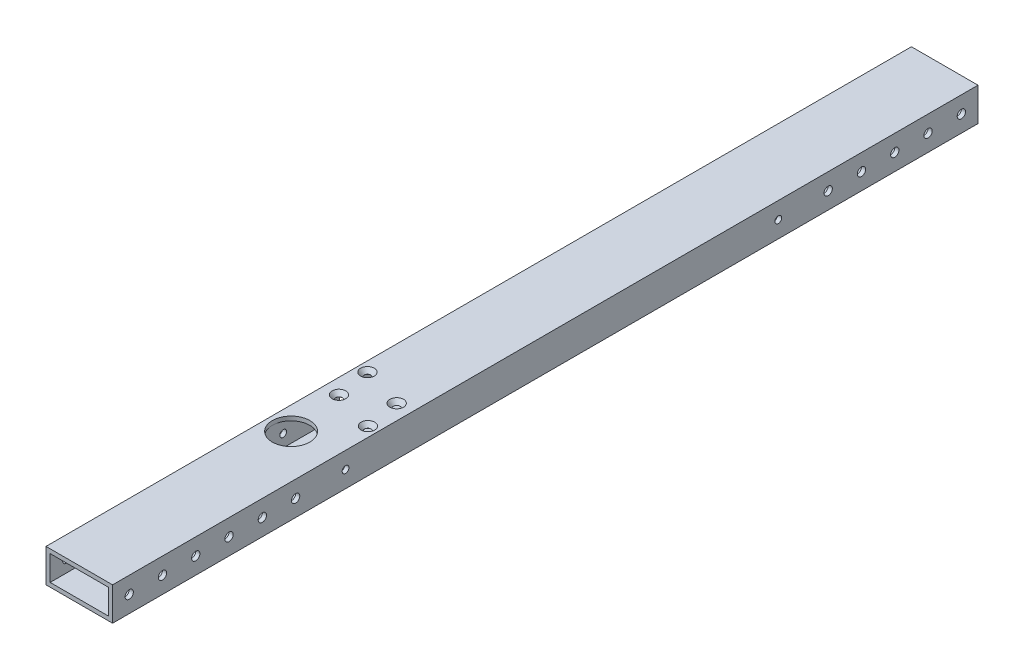
SolidWorks part; units mm, degrees
material "6061 Alloy"
ref_plane "Front Plane" through (0, 0, 0) normal (0, 0, 1) x (1, 0, 0)
ref_plane "Top Plane" through (0, 0, 0) normal (0, 1, 0) x (1, 0, 0)
ref_plane "Right Plane" through (0, 0, 0) normal (1, 0, 0) x (0, 0, -1)
sketch "Sketch1" plane through (0, 0, 0) normal (0, 0, 1) x (1, 0, 0)
  line L0 (-22.225, 9.525) -> (22.225, 9.525)
  line L2 (-25.4, 12.7) -> (25.4, 12.7)
  line L3 (-25.4, 12.7) -> (-25.4, -12.7)
  line L4 (-25.4, -12.7) -> (25.4, -12.7)
  line L5 (25.4, 12.7) -> (25.4, -12.7)
  line L10 (22.225, 9.525) -> (22.225, -9.525)
  line L11 (-22.225, -9.525) -> (22.225, -9.525)
  line L12 (-22.225, 9.525) -> (-22.225, -9.525)
  point P12 (0, 12.7)
  point P14 (25.4, 0)
  dimension "Wall Thickness" = 3.175
  dimension "Outside Width" = 50.8
  dimension "Outside Height" = 25.4
  dimension "Inside Height" = 19.05
  dimension "Inside Width" = 44.45
sketch "Sketch2" plane through (0, 0, 0) normal (1, 0, 0) x (0, 0, -1)
  line L0 (330.2, 0) -> (-330.2, 0)
  point P4 (0, 0)
  point P7 (-330.2, 0)
  point P10 (330.2, 0)
  dimension "Length" = 660.4
sketch "Sketch3" plane through (0, 0, 0) normal (0, 0, 1) x (1, 0, 0)
  line L21 (25.4, 12.7) -> (-25.4, 12.7)
  line L22 (25.4, -12.7) -> (25.4, 12.7)
  line L23 (-25.4, -12.7) -> (25.4, -12.7)
  line L24 (-25.4, 12.7) -> (-25.4, -12.7)
  line L25 (25.4, 12.7) -> (-25.4, 12.7)
  line L26 (25.4, -12.7) -> (25.4, 12.7)
  line L27 (-25.4, -12.7) -> (25.4, -12.7)
  line L28 (-25.4, 12.7) -> (-25.4, -12.7)
  line L29 (22.225, 9.525) -> (-22.225, 9.525)
  line L30 (22.225, -9.525) -> (22.225, 9.525)
  line L31 (-22.225, -9.525) -> (22.225, -9.525)
  line L32 (-22.225, 9.525) -> (-22.225, -9.525)
  line L33 (22.225, 9.525) -> (-22.225, 9.525)
  line L34 (22.225, -9.525) -> (22.225, 9.525)
  line L35 (-22.225, -9.525) -> (22.225, -9.525)
  line L36 (-22.225, 9.525) -> (-22.225, -9.525)
  dimension "D1" = 0
  dimension "D2" = 0
extrude "Boss-Extrude1" add sketch "Sketch3" along normal up to vertex (330.2 mm away) and the other way up to vertex (330.2 mm away) up to point (0, 0, 330.2) other way up to point (0, 0, -330.2)
sketch "Drawing Reference" plane through (0, 0, 0) normal (1, 0, 0) x (0, 0, -1)
  line L0 (-330.2, 0) -> (330.2, 0) construction
  line L1 (0, -12.7) -> (0, 12.7) construction
  line L2 (-330.2, -12.7) -> (330.2, -12.7) construction
  line L5 (-330.2, 12.7) -> (330.2, 12.7) construction
  point P7 (-293.624, 0)
  point P8 (293.624, 0)
  dimension "D1" = 36.576
sketch "Sketch5" plane through (25.4, 0, 0) normal (1, 0, 0) x (0, 0, -1)
  line L2 (-266.7, 0) -> (-241.3, 0)
  line L3 (-241.3, 0) -> (-215.9, 0)
  line L4 (-215.9, 0) -> (-190.5, 0)
  line L5 (-317.5, 0) -> (-330.2, 0)
  line L6 (-330.2, -12.7) -> (-330.2, 12.7) construction
  line L7 (-317.5, 0) -> (-292.1, 0)
  line L8 (-292.1, 0) -> (-266.7, 0)
sketch "Sketch8" plane through (25.4, 0, 0) normal (1, 0, 0) x (0, 0, -1)
  line L0 (330.2, 0) -> (292.1, 0)
  line L1 (330.2, -12.7) -> (330.2, 12.7) construction
  line L2 (292.1, 0) -> (266.7, 0)
  line L3 (266.7, 0) -> (241.3, 0)
  line L4 (241.3, 0) -> (215.9, 0)
  line L5 (330.2, 0) -> (317.5, 0)
hole_wizard "1/4 (0.25) Diameter Hole3" positions "Sketch12" profile "Sketch13" hole size "1/4" standard "ANSI Inch" end condition through all
sketch "Sketch12" plane through (-25.4, 0, 0) normal (-1, 0, 0) x (0, 0, 1)
  point P4 (-317.5, 0)
sketch "Sketch13" plane through (-25.4, 0, -317.5) normal (0, 1, 0) x (0, 0, 1)
  line L0 (0, 0) -> (0, 50.8)
  line L1 (0, 50.8) -> (3.175, 50.8)
  line L2 (3.175, 50.8) -> (3.175, 0)
  line L5 (3.175, 0) -> (0, 0)
  line L11 (0, -6.35) -> (0, 107.95) construction
  dimension "Thru Hole Dia." = 6.35
  dimension "Thru Hole Depth" = 50.8
hole_wizard "1/4 (0.25) Diameter Hole4" positions "Sketch14" profile "Sketch15" hole size "1/4" standard "ANSI Inch" end condition through all
sketch "Sketch14" plane through (-25.4, 0, 0) normal (-1, 0, 0) x (0, 0, 1)
  point P0 (292.1, 0)
  point P3 (317.5, 0)
sketch "Sketch15" plane through (-25.4, 0, 292.1) normal (0, 1, 0) x (0, 0, 1)
  line L0 (0, 0) -> (0, 50.8)
  line L1 (0, 50.8) -> (3.175, 50.8)
  line L2 (3.175, 50.8) -> (3.175, 0)
  line L5 (3.175, 0) -> (0, 0)
  line L11 (0, -6.35) -> (0, 107.95) construction
  dimension "Thru Hole Dia." = 6.35
  dimension "Thru Hole Depth" = 50.8
hole_wizard "1/4 (0.25) Diameter Hole5" positions "Sketch17" profile "Sketch18" hole size "1/4" standard "ANSI Inch" end condition through all
sketch "Sketch17" plane through (25.4, 0, 0) normal (1, 0, 0) x (0, 0, -1)
  point P0 (292.1, 0)
  point P3 (266.7, 0)
sketch "Sketch18" plane through (25.4, 0, -292.1) normal (0, 1, 0) x (0, 0, -1)
  line L0 (0, 0) -> (0, 50.8)
  line L1 (0, 50.8) -> (3.175, 50.8)
  line L2 (3.175, 50.8) -> (3.175, 0)
  line L5 (3.175, 0) -> (0, 0)
  line L11 (0, -6.35) -> (0, 107.95) construction
  dimension "Thru Hole Dia." = 6.35
  dimension "Thru Hole Depth" = 50.8
hole_wizard "1/4 (0.25) Diameter Hole6" positions "Sketch19" profile "Sketch20" hole size "1/4" standard "ANSI Inch" end condition through all
sketch "Sketch19" plane through (25.4, 0, 0) normal (1, 0, 0) x (0, 0, -1)
  point P0 (215.9, 0)
  point P3 (241.3, 0)
sketch "Sketch20" plane through (25.4, 0, -215.9) normal (0, 1, 0) x (0, 0, -1)
  line L0 (0, 0) -> (0, 50.8)
  line L1 (0, 50.8) -> (3.175, 50.8)
  line L2 (3.175, 50.8) -> (3.175, 0)
  line L5 (3.175, 0) -> (0, 0)
  line L11 (0, -6.35) -> (0, 107.95) construction
  dimension "Thru Hole Dia." = 6.35
  dimension "Thru Hole Depth" = 50.8
hole_wizard "1/4 (0.25) Diameter Hole7" positions "Sketch21" profile "Sketch22" hole size "1/4" standard "ANSI Inch" end condition through all
sketch "Sketch21" plane through (25.4, 0, 0) normal (1, 0, 0) x (0, 0, -1)
  point P0 (-190.5, 0)
  point P3 (-215.9, 0)
sketch "Sketch22" plane through (25.4, 0, 190.5) normal (0, 1, 0) x (0, 0, -1)
  line L0 (0, 0) -> (0, 50.8)
  line L1 (0, 50.8) -> (3.175, 50.8)
  line L2 (3.175, 50.8) -> (3.175, 0)
  line L5 (3.175, 0) -> (0, 0)
  line L11 (0, -6.35) -> (0, 107.95) construction
  dimension "Thru Hole Dia." = 6.35
  dimension "Thru Hole Depth" = 50.8
hole_wizard "1/4 (0.25) Diameter Hole8" positions "Sketch23" profile "Sketch24" hole size "1/4" standard "ANSI Inch" end condition through all
sketch "Sketch23" plane through (25.4, 0, 0) normal (1, 0, 0) x (0, 0, -1)
  point P0 (-266.7, 0)
  point P3 (-241.3, 0)
sketch "Sketch24" plane through (25.4, 0, 266.7) normal (0, 1, 0) x (0, 0, -1)
  line L0 (0, 0) -> (0, 50.8)
  line L1 (0, 50.8) -> (3.175, 50.8)
  line L2 (3.175, 50.8) -> (3.175, 0)
  line L5 (3.175, 0) -> (0, 0)
  line L11 (0, -6.35) -> (0, 107.95) construction
  dimension "Thru Hole Dia." = 6.35
  dimension "Thru Hole Depth" = 50.8
sketch "Sketch25" plane through (25.4, 0, 0) normal (1, 0, 0) x (0, 0, -1)
  line L0 (-190.5, 0) -> (-152.4, 0)
  line L1 (215.9, 0) -> (177.8, 0)
hole_wizard "13/64 (0.20313) Diameter Hole1" positions "Sketch26" profile "Sketch27" hole size "13/64" standard "ANSI Inch" end condition through all
sketch "Sketch26" plane through (25.4, 0, 0) normal (1, 0, 0) x (0, 0, -1)
  point P0 (-152.4, 0)
  point P3 (177.8, 0)
sketch "Sketch27" plane through (25.4, 0, 152.4) normal (0, 1, 0) x (0, 0, -1)
  line L0 (0, 0) -> (0, 50.8)
  line L1 (0, 50.8) -> (2.5798, 50.8)
  line L2 (2.5798, 50.8) -> (2.5798, 0)
  line L5 (2.5798, 0) -> (0, 0)
  line L11 (0, -6.35) -> (0, 107.95) construction
  dimension "Thru Hole Dia." = 5.1595
  dimension "Thru Hole Depth" = 50.8
sketch "Sketch30" plane through (-25.4, 0, 0) normal (-1, 0, 0) x (0, 0, 1)
  point P0 (-128.5875, 0)
  point P1 (-103.1875, 0)
  point P2 (77.7875, 0)
  point P3 (103.1875, 0)
hole_wizard "1/2 (0.5) Diameter Hole1" positions "Sketch33" profile "Sketch34" hole size "1/2" standard "ANSI Inch"
sketch "Sketch33" plane through (-25.4, 0, 0) normal (-1, 0, 0) x (0, 0, 1)
  point P0 (-128.5875, 0)
  point P3 (-103.1875, 0)
  point P7 (77.7875, 0)
  point P10 (103.1875, 0)
sketch "Sketch34" plane through (-25.4, 0, -128.5875) normal (0, 1, 0) x (0, 0, 1)
  line L0 (0, 0) -> (0, 10.1655)
  line L1 (0, 10.1655) -> (6.35, 6.35)
  line L2 (6.35, 6.35) -> (6.35, 0)
  line L5 (6.35, 0) -> (0, 0)
  line L10 (0, 10.1655) -> (-6.35, 6.35) construction
  line L11 (0, -6.35) -> (0, 107.95) construction
  dimension "Hole Dia." = 12.7
  dimension "Hole Depth" = 6.35
  dimension "Drill Angle" = 118
sketch "Sketch37" plane through (0, -12.7, 0) normal (0, -1, 0) x (1, 0, 0)
  line L1 (13.819, 101.7821) -> (17.931, 127.883) construction
  line L5 (-13.819, 118.2319) -> (17.931, 127.883) construction
  line L6 (-17.931, 92.3773) -> (13.819, 101.7821) construction
  line L7 (-13.819, 118.2319) -> (-17.931, 92.3773) construction
hole_wizard "#10 Clearance Hole4" positions "Sketch45" profile "Sketch46" hole size "#10" standard "ANSI Inch" end condition through all
sketch "Sketch45" plane through (0, -12.7, 0) normal (0, -1, 0) x (-1, 0, 0)
  point P0 (-13.819, -101.7821)
  point P3 (-17.931, -127.883)
  point P6 (13.819, -118.2319)
  point P9 (17.931, -92.3773)
sketch "Sketch46" plane through (13.819, -12.7, 101.7821) normal (1, 0, 0) x (0, 0, -1)
  line L0 (0, 0) -> (0, 25.4)
  line L1 (0, 25.4) -> (5.2197, 25.4)
  line L2 (2.4892, 22.2589) -> (2.4892, 0)
  line L5 (2.4892, 0) -> (0, 0)
  line L7 (5.2197, 25.4) -> (2.4892, 22.2589)
  line L8 (-5.2197, 25.4) -> (-2.4892, 22.2589) construction
  line L11 (0, -6.35) -> (0, 107.95) construction
  dimension "Thru Hole Dia." = 4.9784
  dimension "Thru Hole Depth" = 25.4
  dimension "Far C'Sink Dia." = 10.4394
  dimension "Far C'Sink Angle" = 82
sketch "Sketch47" plane through (0, -12.7, 0) normal (0, -1, 0) x (1, 0, 0)
  line L0 (25.4, 144.0217) -> (-25.4, 128.9741) construction
  line L1 (25.4, 330.2) -> (25.4, -330.2) construction
  line L2 (-25.4, 128.9741) -> (575.1111, 306.8536) construction
  line L3 (-25.4, 128.9741) -> (-25.4, 180.922) construction
  line L4 (-25.4, 330.2) -> (-25.4, -330.2) construction
  line L5 (-22.225, 128.9741) -> (-22.225, 180.922) construction
  line L6 (22.2439, 154.6766) -> (-28.5561, 139.629) construction
  circle A0 centre (-7.9375, 160.6376) radius 14.2875
  dimension "D1" = 3.175
  dimension "D2" = 11.1125
extrude "Cut-Extrude1" cut sketch "Sketch47" against normal through all
equation "\"D1@Drawing Reference\"=\"Outside Width@Sketch1\" * 0.72"
